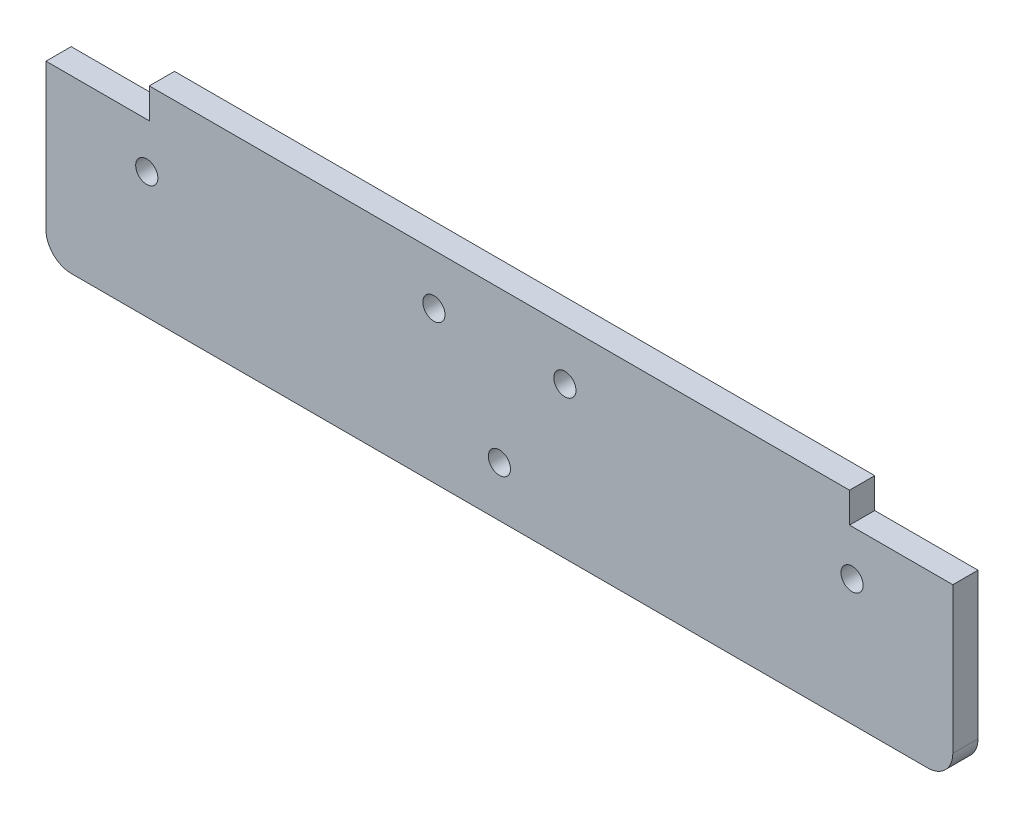
SolidWorks part; units mm, degrees
ref_plane "Płaszczyzna przednia" through (0, 0, 0) normal (0, 0, 1) x (1, 0, 0)
ref_plane "Płaszczyzna górna" through (0, 0, 0) normal (0, 1, 0) x (1, 0, 0)
ref_plane "Płaszczyzna prawa" through (0, 0, 0) normal (1, 0, 0) x (0, 0, -1)
sketch "Szkic1" plane through (0, 0, 0) normal (0, 0, 1) x (1, 0, 0)
  line L1 (-90, -20) -> (90, -20)
  line L2 (-90, -20) -> (-90, 20)
  line L3 (-90, 20) -> (90, 20)
  line L4 (90, -20) -> (90, 20)
  line L5 (-90, -20) -> (90, 20) construction
  line L6 (-90, 20) -> (90, -20) construction
  point P0 (0, 0)
  dimension "D1" = 40
  dimension "D2" = 180
extrude "Dodanie-wyciągnięcie1" add sketch "Szkic1" along normal blind 5
fillet "Zaokrąglenie1" radius 5 4 edges at (-90, 20, 2.5) (-90, -20, 2.5) (90, -20, 2.5) (90, 20, 2.5)
sketch "Szkic2" plane through (0, 0, 5) normal (0, 0, 1) x (1, 0, 0)
  line L0 (-90, 15) -> (-90, -15) construction
  line L1 (90, -15) -> (90, 15) construction
  line L2 (85, 20) -> (-85, 20) construction
  circle A0 centre (-70, 5) radius 2.2
  circle A1 centre (-13, 10) radius 2.2
  circle A2 centre (13, 10) radius 2.2
  circle A3 centre (70, 5) radius 2.2
  dimension "D1" = 26
  dimension "D4" = 20
  dimension "D6" = 4.4
  dimension "D7" = 10
  dimension "D2" = 13
  dimension "D3" = 20
  dimension "D5" = 15
extrude "Wytnij-wyciągnięcie1" cut sketch "Szkic2" against normal blind 5
sketch "Szkic3" plane through (0, 0, 5) normal (0, 0, 1) x (1, 0, 0)
  line L0 (-90, 15) -> (-90, -15) construction
  line L1 (-90, 20) -> (-69.5, 20)
  line L2 (-90, 20) -> (-90, 14)
  line L3 (-90, 14) -> (-69.5, 14)
  line L4 (-69.5, 20) -> (-69.5, 14)
  line L5 (85, 20) -> (-85, 20) construction
  line L6 (90, -15) -> (90, 15) construction
  line L7 (90, 20) -> (69.5, 20)
  line L8 (90, 20) -> (90, 14)
  line L9 (90, 14) -> (69.5, 14)
  line L10 (69.5, 20) -> (69.5, 14)
  dimension "D1" = 6
  dimension "D2" = 20.5
  dimension "D3" = 6
extrude "Wytnij-wyciągnięcie2" cut sketch "Szkic3" against normal blind 10
sketch "Szkic4" plane through (0, 0, 5) normal (0, 0, 1) x (1, 0, 0)
  line L0 (-85, -20) -> (85, -20) construction
  circle A0 centre (0, -10) radius 2.2
  point P4 (0, 0)
  point P5 (0, -20)
  dimension "D1" = 10
  dimension "D2" = 4.4
extrude "Wytnij-wyciągnięcie3" cut sketch "Szkic4" against normal blind 10
